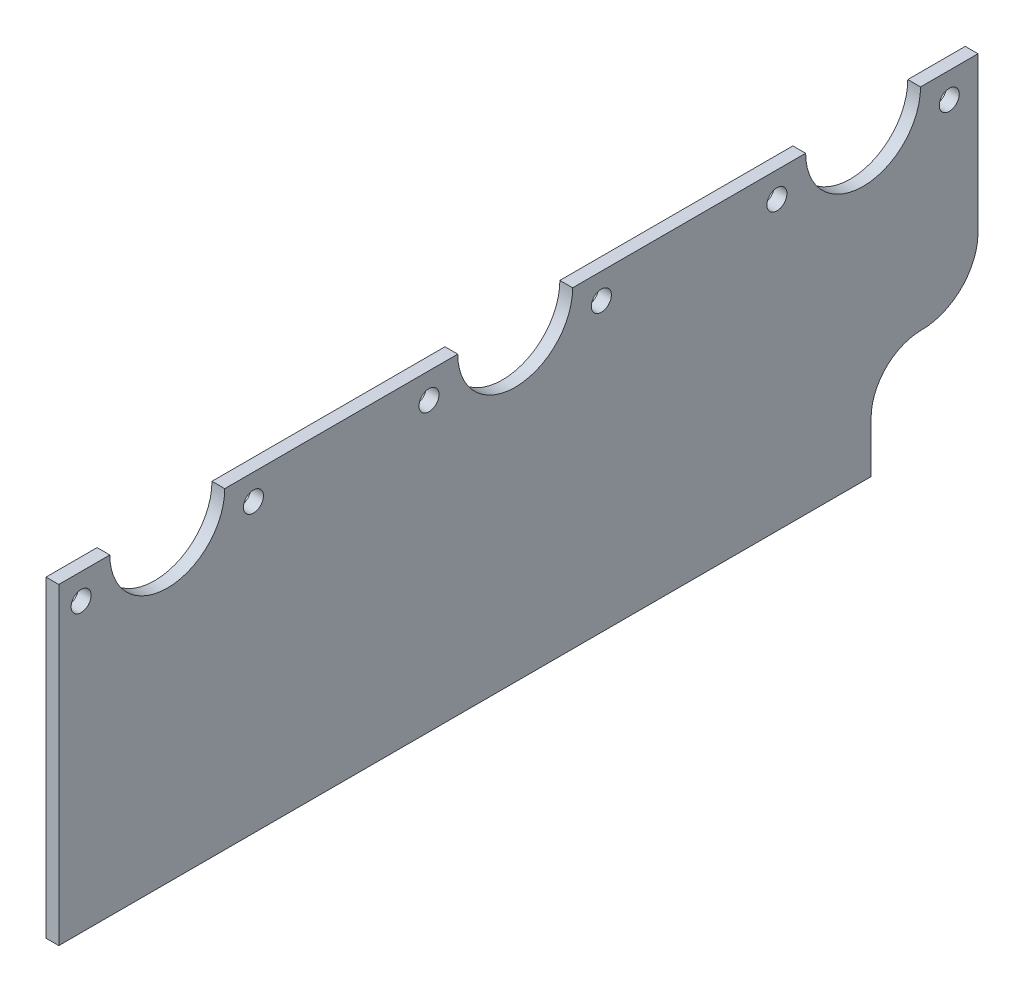
SolidWorks part; units mm, degrees
material "6061 Alloy"
ref_plane "Front Plane" through (0, 0, 0) normal (0, 0, 1) x (1, 0, 0)
ref_plane "Top Plane" through (0, 0, 0) normal (0, 1, 0) x (1, 0, 0)
ref_plane "Right Plane" through (0, 0, 0) normal (1, 0, 0) x (0, 0, -1)
sketch "Sketch1" plane through (0, 0, 0) normal (1, 0, 0) x (0, 0, -1)
  line L0 (114.3, 0) -> (-114.3, 0)
  line L1 (-114.3, 0) -> (-114.3, 77.7875)
  line L2 (-114.3, 77.7875) -> (-101.6, 77.7875)
  line L3 (-73.025, 77.7875) -> (-15.0812, 77.7875)
  line L4 (13.4938, 77.7875) -> (71.4375, 77.7875)
  line L5 (100.0125, 77.7875) -> (114.3, 77.7875)
  line L6 (114.3, 77.7875) -> (114.3, 0)
  line L7 (-114.3, 25.4) -> (114.3, 25.4) construction
  arc A6 (-101.6, 77.7875) -> (-73.025, 77.7875) centre (-87.3125, 77.7875) ccw
  arc A7 (-15.0812, 77.7875) -> (13.4938, 77.7875) centre (-0.7937, 77.7875) ccw
  arc A8 (71.4375, 77.7875) -> (100.0125, 77.7875) centre (85.725, 77.7875) ccw
  point P4 (0, 0)
  dimension "D1" = 25.4
  dimension "D3" = 14.2875
  dimension "D5" = 28.575
  dimension "D6" = 38.1
  dimension "D2" = 228.6
  dimension "D4" = 12.7
extrude "Boss-Extrude1" add sketch "Sketch1" along normal blind 3.175
hole_wizard "#10 Clearance Hole1" positions "Sketch2" profile "Sketch3" hole size "#10" standard "ANSI Inch" end condition through all
sketch "Sketch2" plane through (3.175, 0, 0) normal (1, 0, 0) x (0, 0, -1)
  line L0 (-108.7437, 71.4375) -> (-65.8812, 71.4375) construction
  line L2 (-22.225, 71.4375) -> (20.6375, 71.4375) construction
  line L4 (64.2938, 71.4375) -> (107.1563, 71.4375) construction
  line L6 (-101.6, 77.7875) -> (-114.3, 77.7875) construction
  line L7 (-87.3125, 71.4375) -> (-87.3125, 77.7875) construction
  line L9 (-0.7937, 77.7875) -> (-0.7937, 71.4375) construction
  line L11 (85.725, 77.7875) -> (85.725, 71.4375) construction
  point P0 (-108.7437, 71.4375)
  point P2 (-65.8812, 71.4375)
  point P4 (-22.225, 71.4375)
  point P6 (20.6375, 71.4375)
  point P8 (64.2938, 71.4375)
  point P10 (107.1563, 71.4375)
  dimension "D1" = 42.8625
  dimension "D2" = 6.35
sketch "Sketch3" plane through (3.175, 71.4375, 108.7437) normal (0, 1, 0) x (0, 0, -1)
  line L0 (0, 0) -> (0, 3.175)
  line L1 (0, 3.175) -> (2.4892, 3.175)
  line L2 (2.4892, 3.175) -> (2.4892, 0)
  line L5 (2.4892, 0) -> (0, 0)
  line L11 (0, -6.35) -> (0, 107.95) construction
  dimension "Thru Hole Dia." = 4.9784
  dimension "Thru Hole Depth" = 3.175
sketch "Sketch4" plane through (0, 0, 0) normal (-1, 0, 0) x (0, 0, 1)
  line L1 (-87.9729, 12.7) -> (-87.9729, 0) construction
  line L2 (114.3, 0) -> (-114.3, 0) construction
  line L3 (-114.3, 25.4) -> (-106.8754, 25.4) construction
  line L4 (-114.3, 0) -> (-114.3, 77.7875) construction
  line L5 (-100.33, 25.0571) -> (-106.8754, 25.4) construction
  line L6 (-114.3, 25.4) -> (-114.3, 0) construction
  line L7 (-114.3, 0) -> (-87.9729, 0) construction
  line L10 (-87.7189, 12.7) -> (-87.7189, 0)
  line L13 (-100.3233, 25.3111) -> (-106.8688, 25.654) construction
  line L14 (-114.554, 25.654) -> (-106.8688, 25.654) construction
  line L15 (-114.554, 25.654) -> (-114.554, -0.254) construction
  line L16 (-114.554, -0.254) -> (-87.7189, -0.254) construction
  line L17 (-114.3, 38.8937) -> (-114.3, 0)
  line L18 (-114.3, 0) -> (-87.7189, 0)
  line L20 (-87.7189, 12.7) -> (-87.7189, -0.254) construction
  arc A1 (-106.8754, 25.4) -> (-106.8754, 0) centre (-100.33, 12.7) ccw construction
  circle A2 centre (-100.33, 12.7) radius 12.3571 construction
  arc A3 (-106.8754, 25.4) -> (-106.8754, 0) centre (-100.33, 12.7) ccw construction
  arc A4 (-87.9729, 12.7) -> (-100.33, 25.0571) centre (-100.33, 12.7) ccw construction
  arc A5 (-87.7189, 12.7) -> (-100.3233, 25.3111) centre (-100.33, 12.7) ccw
  arc A6 (-100.3233, 25.3111) -> (-114.3, 38.8937) centre (-100.3159, 39.3011) cw
  dimension "D1" = 0.254
extrude "Cut-Extrude1" cut sketch "Sketch4" against normal through all
